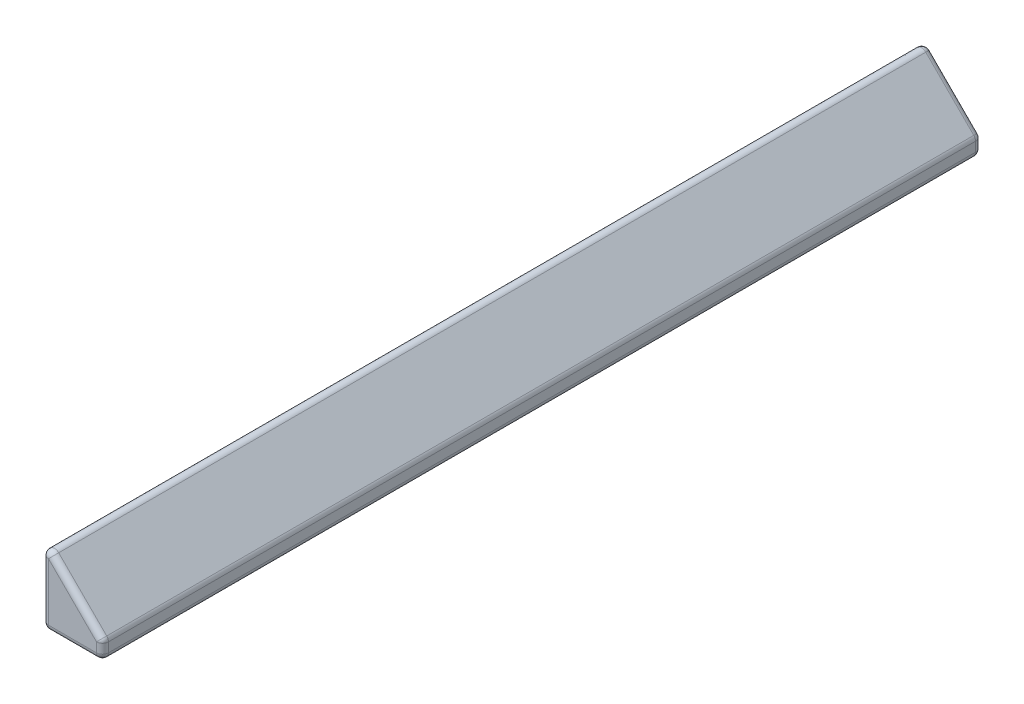
SolidWorks part; units mm, degrees
material "6061-T6 (SS)"
ref_plane "Front Plane" through (0, 0, 0) normal (0, 0, 1) x (1, 0, 0)
ref_plane "Top Plane" through (0, 0, 0) normal (0, 1, 0) x (1, 0, 0)
ref_plane "Right Plane" through (0, 0, 0) normal (1, 0, 0) x (0, 0, -1)
sketch "Sketch1" plane through (0, 0, 0) normal (0, 0, 1) x (1, 0, 0)
  line L5 (0, 0) -> (2.6, 0)
  line L6 (2.6, 0) -> (0, 2.6)
  line L7 (0, 2.6) -> (0, 0)
  line L11 (2, 0) -> (2, 0.6)
  dimension "D1" = 0.6
  dimension "D2" = 2.6
extrude "Boss-Extrude1" add sketch "Sketch1" against normal mid plane 29.3 contours L5 L11 L6 L7 region at (0.7917, 0.9042, 0)
fillet "Fillet1" radius 0.2 12 edges at (0, 2.6, 0) (0, 0, 0) (2, 0.6, 0) (2, 0, 0) (2, 0.3, -14.65) (1, 1.6, -14.65) (0, 1.3, -14.65) (1, 0, -14.65) (0, 1.3, 14.65) (1, 1.6, 14.65) (2, 0.3, 14.65) (1, 0, 14.65)
